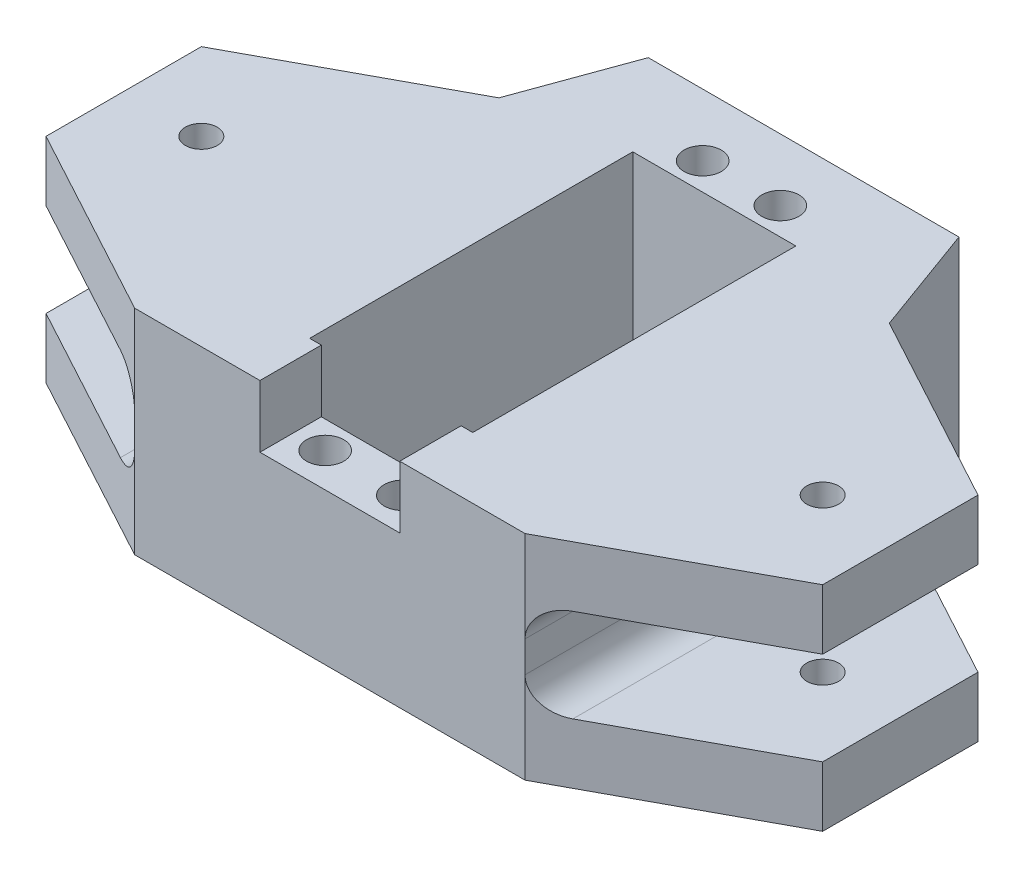
SolidWorks part; units mm, degrees
ref_plane "Front Plane" through (0, 0, 0) normal (0, 0, 1) x (1, 0, 0)
ref_plane "Top Plane" through (0, 0, 0) normal (0, 1, 0) x (1, 0, 0)
ref_plane "Right Plane" through (0, 0, 0) normal (1, 0, 0) x (0, 0, -1)
sketch "Sketch1" plane through (0, 0, 0) normal (0, 1, 0) x (1, 0, 0)
  line L0 (0, 0) -> (0, 55585.7092) construction
  line L1 (0, 0) -> (55585.7092, 0) construction
  line L2 (20, 37.5477) -> (-20, 37.5477)
  line L3 (-20, 37.5477) -> (-25.1303, 23.4523)
  line L4 (-25.1303, 23.4523) -> (-50, 10)
  line L5 (-50, 10) -> (-50, -10)
  line L11 (50, 10) -> (50, -10)
  line L12 (25.1303, 23.4523) -> (50, 10)
  line L13 (20, 37.5477) -> (25.1303, 23.4523)
  line L14 (25.1303, -23.4523) -> (50, -10)
  line L15 (-25.1303, -23.4523) -> (-50, -10)
  line L19 (25.1303, -23.4523) -> (-25.1303, -23.4523)
  point P7 (50, 0)
  point P12 (-50, 0)
  point P14 (0, -10.7407)
  point P19 (0, 37.5477)
  dimension "D1" = 40
  dimension "D2" = 20
  dimension "D3" = 61
  dimension "D4" = 100
  dimension "D5" = 110
  dimension "D8" = 15
extrude "Main-Body" add sketch "Sketch1" along normal mid plane 27.5
sketch "Sketch2" plane through (0, 13.75, 0) normal (0, 1, 0) x (1, 0, 0)
  line L0 (0, 47.5477) -> (0, -49952.4523) construction
  line L2 (20, 37.5477) -> (-20, 37.5477) construction
  line L3 (-6.4366, -21.4523) -> (49993.5634, -21.4523) construction
  line L4 (10.5, -15.5523) -> (-10.5, -15.5523)
  line L5 (-10.5, -15.5523) -> (-10.5, 26.0477)
  line L6 (-10.5, 26.0477) -> (10.5, 26.0477)
  line L7 (10.5, -15.5523) -> (10.5, 26.0477)
  line L8 (0, -23.4523) -> (50000, -23.4523) construction
  line L10 (-5, 29.5477) -> (5, 29.5477) construction
  line L11 (-5, -19.0523) -> (5, -19.0523) construction
  line L12 (-25.1303, -23.4523) -> (25.1303, -23.4523) construction
  circle A0 centre (-5, -19.0523) radius 2.4
  circle A1 centre (5, -19.0523) radius 2.4
  circle A2 centre (-5, 29.5477) radius 2.4
  circle A3 centre (5, 29.5477) radius 2.4
  point P22 (0, -15.5523)
  point P23 (0, 26.0477)
  point P28 (0, 37.5477)
  point P29 (0, -19.0523)
  point P30 (0, 29.5477)
  dimension "D1" = 4.8
  dimension "D4" = 4.8
  dimension "D10" = 4.8
  dimension "D11" = 4.8
  dimension "D3" = 10
  dimension "D5" = 48.6
  dimension "D6" = 10
  dimension "D7" = 21
  dimension "D8" = 3.5
  dimension "D9" = 3.5
  dimension "D2" = 2
extrude "Servo-Cutout" cut sketch "Sketch2" against normal blind 30
sketch "Sketch3" plane through (0, 0, 23.4523) normal (0, 0, 1) x (1, 0, 0)
  line L0 (0, 0) -> (0, 50000) construction
  line L1 (0, 0) -> (48695.3801, 0) construction
  line L3 (9, 13.75) -> (-9, 13.75)
  line L4 (-9, 13.75) -> (-9, 5.75)
  line L5 (-9, 5.75) -> (9, 5.75)
  line L6 (9, 13.75) -> (9, 5.75)
  line L7 (-25.1303, 13.75) -> (25.1303, 13.75) construction
  point P10 (0, 0)
  point P11 (0, 13.75)
  dimension "D1" = 18
  dimension "D2" = 8
  dimension "D3" = 0
extrude "Servo-Cable-Cutout" cut sketch "Sketch3" against normal up to surface (7.9 mm away) up to face at (0, 0, 15.5523)
sketch "Sketch4" plane through (0, 0, 23.4523) normal (0, 0, 1) x (1, 0, 0)
  line L0 (0, 0) -> (0, 50000) construction
  line L1 (50, 0) -> (50050, 0) construction
  line L2 (50, 13.75) -> (50, -13.75) construction
  line L3 (-50, -6) -> (-50, 6)
  line L4 (-50, 13.75) -> (-50, -13.75) construction
  line L5 (-50, 6) -> (-25.1303, 6)
  line L6 (-25.1303, 6) -> (-25.1303, -6)
  line L7 (-50, -6) -> (-25.1303, -6)
  line L10 (-25.1303, 13.75) -> (-25.1303, -13.75) construction
  point P7 (50, 0)
  point P15 (-25.1303, 0)
  point P16 (-50, 0)
  dimension "D1" = 0
  dimension "D2" = 12
extrude "Control-Arm-Cutout" cut sketch "Sketch4" against normal through all both and the other way through all
mirror "Mirror1" about plane through (0, 0, 0) normal (1, 0, 0) of "Control-Arm-Cutout"
sketch "Sketch5" plane through (0, 13.75, 0) normal (0, 1, 0) x (1, 0, 0)
  line L0 (-50, 0) -> (49950, 0) construction
  line L1 (-50, 10) -> (-50, -10) construction
  line L2 (0, 0) -> (0, 50000) construction
  circle A0 centre (-40, 0) radius 2.05
  point P4 (-50, 0)
  dimension "D1" = 4.1
  dimension "D2" = 10
extrude "Cut-Extrude4" cut sketch "Sketch5" against normal through all both and the other way through all
mirror "Mirror2" about plane through (0, 0, 0) normal (1, 0, 0) of "Cut-Extrude4"
fillet "Fillet1" radius 4 4 edges at (-25.1303, -6, 0) (-25.1303, 6, 0) (25.1303, -6, 0) (25.1303, 6, 0)
equation "\"D10@Sketch2\"=\"D1@Sketch2\""
equation "\"D11@Sketch2\"=\"D1@Sketch2\""
